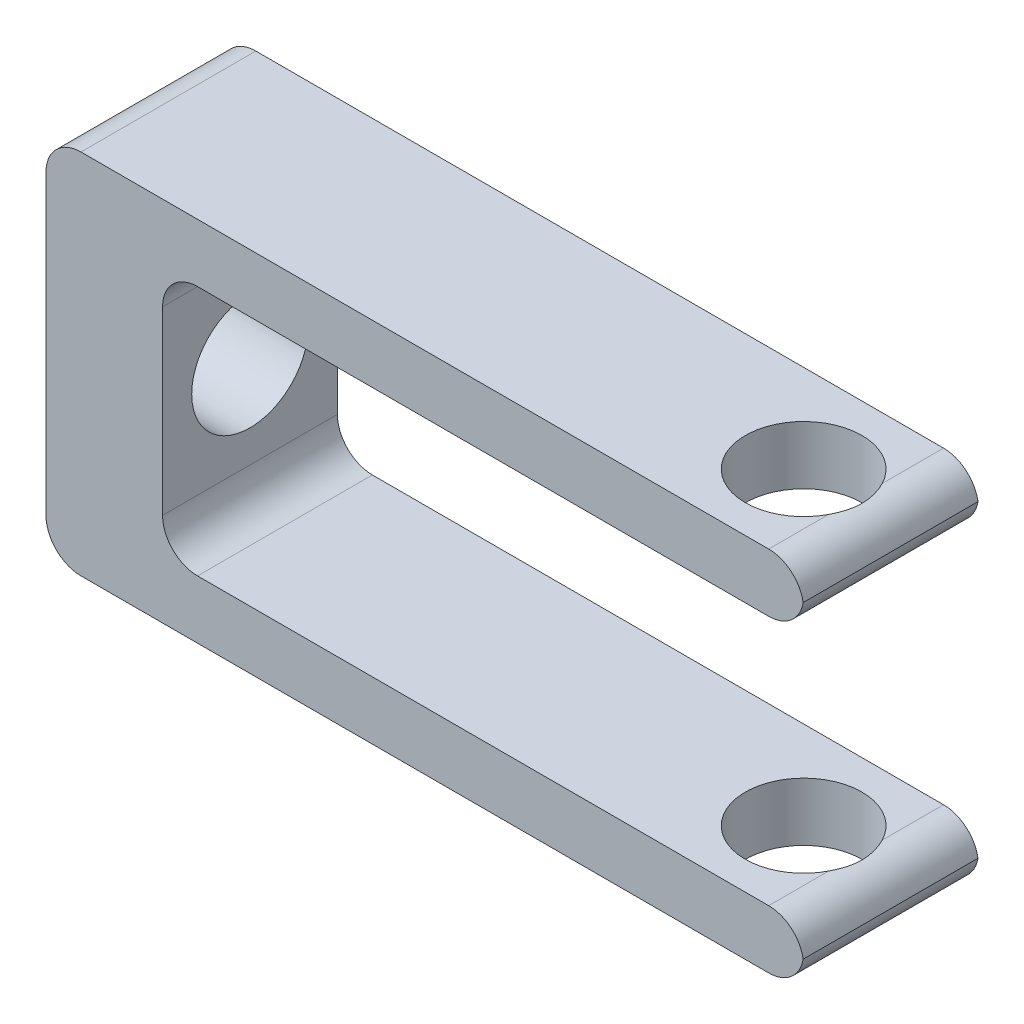
SolidWorks part; units mm, degrees
ref_plane "Front Plane" through (0, 0, 0) normal (0, 0, 1) x (1, 0, 0)
ref_plane "Top Plane" through (0, 0, 0) normal (0, 1, 0) x (1, 0, 0)
ref_plane "Right Plane" through (0, 0, 0) normal (1, 0, 0) x (0, 0, -1)
sketch "Sketch1" plane through (0, 0, 0) normal (1, 0, 0) x (0, 0, -1)
  line L1 (0, 0) -> (19.05, 0)
  line L2 (0, 0) -> (0, 40)
  line L3 (0, 40) -> (19.05, 40)
  line L4 (19.05, 0) -> (19.05, 40)
  dimension "D1" = 19.05
  dimension "D2" = 40
extrude "Boss-Extrude1" add sketch "Sketch1" along normal blind 12.7
sketch "Sketch2" plane through (12.7, 0, 0) normal (1, 0, 0) x (0, 0, -1)
  line L0 (0, 40) -> (19.05, 0) construction
  line L1 (0, 0) -> (0, 6.35)
  line L2 (0, 40) -> (0, 0) construction
  line L3 (0, 6.35) -> (19.05, 6.35)
  line L4 (19.05, 0) -> (19.05, 40) construction
  line L5 (19.05, 6.35) -> (19.05, 0)
  line L7 (19.05, 40) -> (0, 40)
  line L8 (0, 40) -> (0, 33.65)
  line L9 (0, 33.65) -> (19.05, 33.65)
  line L10 (19.05, 33.65) -> (19.05, 40)
  line L11 (19.05, 0) -> (0, 0)
  dimension "D2" = 6.35
  dimension "D3" = 6.35
extrude "Boss-Extrude2" add sketch "Sketch2" along normal blind 69.85
sketch "Sketch5" plane through (0, 0, 0) normal (-1, 0, 0) x (0, 0, 1)
  line L0 (0, 0) -> (-19.05, 40) construction
  circle A0 centre (-9.525, 20) radius 6.35
  dimension "D1" = 12.7
extrude "Cut-Extrude1" cut sketch "Sketch5" against normal up to next
sketch "Sketch6" plane through (0, 0, 0) normal (0, -1, 0) x (1, 0, 0)
  circle A0 centre (73.1, -9.45) radius 6.35
  dimension "D1" = 12.7
extrude "Cut-Extrude2" cut sketch "Sketch6" against normal through all
fillet "Fillet4" radius 3.81 8 edges at (0, 0, -9.525) (0, 40, -9.525) (12.7, 33.65, -9.525) (12.7, 6.35, -9.525) (82.55, 6.35, -9.525) (82.55, 0, -9.525) (82.55, 33.65, -9.525) (82.55, 40, -9.525)
